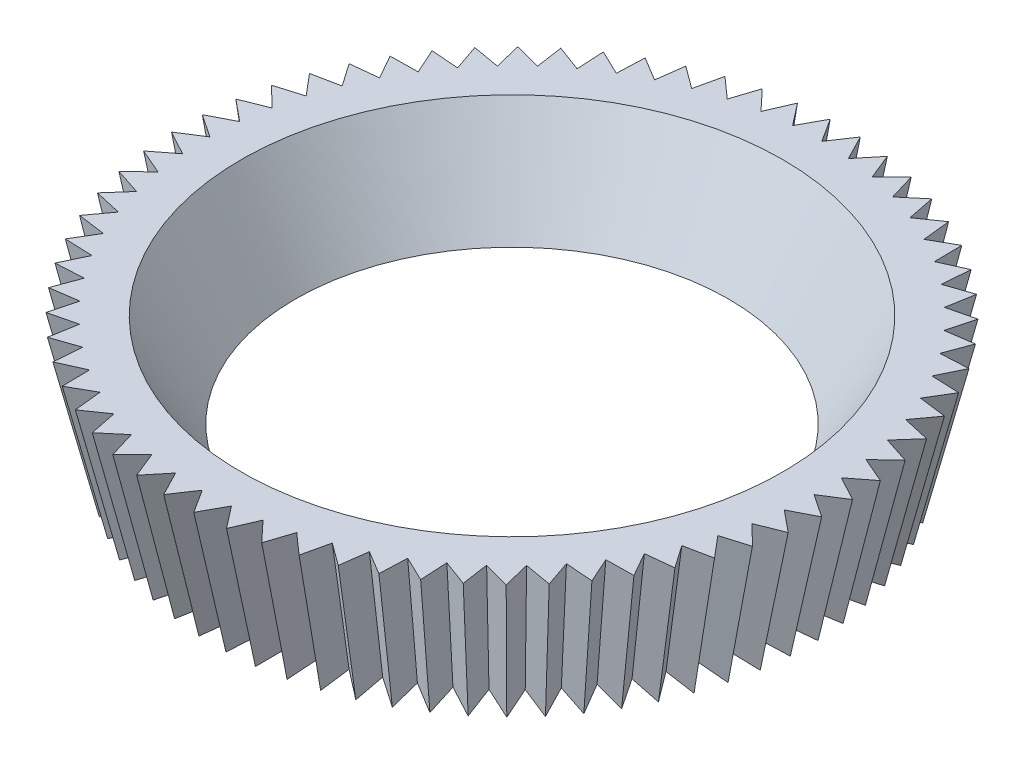
SolidWorks part; units mm, degrees
ref_plane "Front Plane" through (0, 0, 0) normal (0, 0, 1) x (1, 0, 0)
ref_plane "Top Plane" through (0, 0, 0) normal (0, 1, 0) x (1, 0, 0)
ref_plane "Right Plane" through (0, 0, 0) normal (1, 0, 0) x (0, 0, -1)
sketch "Sketch1" plane through (0, 0, 0) normal (0, 0, 1) x (1, 0, 0)
  line L1 (6.1889, 12.0952) -> (7, 13.5)
  line L2 (4.4003, 13.0952) -> (5.5, 15)
  line L4 (0, 12.0952) -> (6.1889, 12.0952) construction
  line L5 (0, 12.0952) -> (0, 15) construction
  line L6 (6.1889, 12.0952) -> (4.4003, 13.0952)
  line L9 (7, 13.5) -> (7, 15)
  line L10 (7, 15) -> (5.5, 15)
  point P3 (3.8102, 11.8914)
  dimension "D1" = 7
  dimension "D2" = 120
  dimension "D3" = 15
  dimension "D4" = 1.5
  dimension "D5" = 1.5
revolve "Revolve1" add sketch "Sketch1" angle 360 about L5
sketch "Sketch2" plane through (0, 15, 0) normal (0, 1, 0) x (1, 0, 0)
  line L0 (0.0575, -6.9998) -> (0.4964, -6.1975)
  line L1 (0.4964, -6.1975) -> (1.0575, -6.9197)
  arc A0 (0.0575, -6.9998) -> (1.0575, -6.9197) centre (0, 0) ccw
  circle A1 centre (0, 0) radius 7 construction
  dimension "D1" = 1
extrude "Cut-Extrude1" cut sketch "Sketch2" against normal through all draft 7 draft outward yes
pattern_circular "CirPattern1" count 68 over 360 about axis through (0, 15, 0) along (0, -1, 0) of "Cut-Extrude1"
